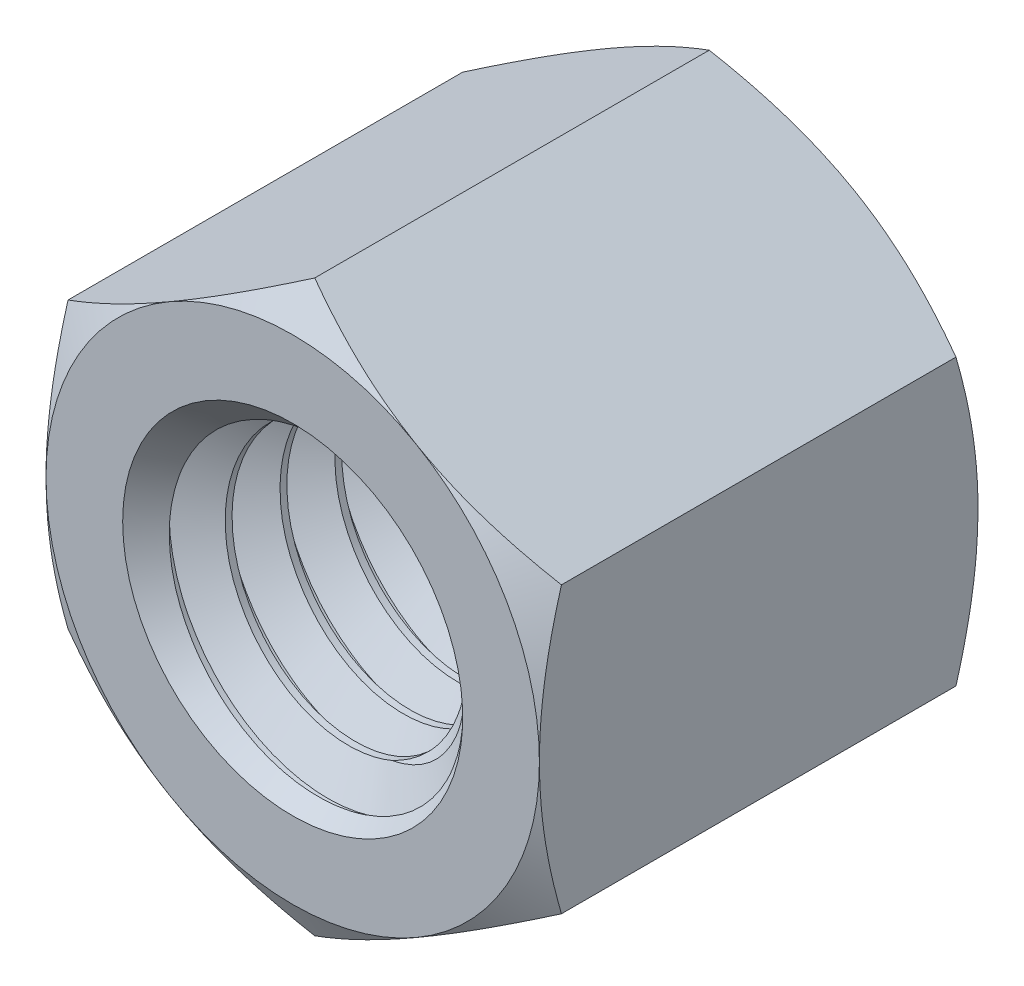
SolidWorks part; units mm, degrees
ref_plane "Front Plane" through (0, 0, 0) normal (0, 0, 1) x (1, 0, 0)
ref_plane "Top Plane" through (0, 0, 0) normal (0, 1, 0) x (1, 0, 0)
ref_plane "Right Plane" through (0, 0, 0) normal (1, 0, 0) x (0, 0, -1)
sketch "Sketch3" plane through (0, 0, 0) normal (1, 0, 0) x (0, 0, -1)
  line L0 (-2, 0) -> (2, 0) construction
  line L1 (0, 2.25) -> (0, -2.25) construction
  line L2 (-2, 1.5) -> (-2, -1.5) construction
  point P2 (-10.7, 0)
  point P3 (10.7, 0)
  dimension "D1" = 12.7
  dimension "Length" = 4
  dimension "Min Thread Length" = 12.7
  dimension "Thread Dia" = 3
  dimension "Hex" = 4.5
sketch "Sketch1" plane through (0, 0, 0) normal (0, 0, 1) x (1, 0, 0)
  line L1 (0, 2.5981) -> (-2.25, 1.299)
  line L2 (-2.25, 1.299) -> (-2.25, -1.299)
  line L3 (-2.25, -1.299) -> (0, -2.5981)
  line L4 (0, -2.5981) -> (2.25, -1.299)
  line L5 (2.25, -1.299) -> (2.25, 1.299)
  line L6 (2.25, 1.299) -> (0, 2.5981)
  circle A0 centre (0, 0) radius 2.25 construction
  circle A1 centre (0, 0) radius 1.5
extrude "Extrude1" add sketch "Sketch1" along normal up to vertex (2 mm away) and the other way up to vertex (2 mm away) up to point (0, 0, 2) other way up to point (0, 0, -2)
sketch "Sketch11" plane through (0, 0, -2) normal (0, 0, -1) x (-1, 0, 0)
  circle A0 centre (0, 0) radius 1.5 construction
  circle A1 centre (0, 0) radius 1.5
curve "Helix/Spiral1" pitch 0.5 height 4.5 radius 1.5 centre (0, 0, -2) axis (0, 0, 1) start towards (0, 1, 0) parameters "Pitch"=0.5
sketch "Sketch12" plane through (0, 0, 0) normal (1, 0, 0) x (0, 0, -1)
  line L0 (2.4375, 1.5) -> (2, 1.5)
  line L1 (2.4375, 1.5) -> (2.25, 1.1752)
  line L2 (2.25, 1.1752) -> (2.1875, 1.1752)
  line L3 (2.1875, 1.1752) -> (2, 1.5)
  line L4 (2.2188, 1.1752) -> (2.2188, 1.5) construction
  line L5 (2.3438, 1.3376) -> (2.0938, 1.3376) construction
  dimension "D1" = 0.0625
  dimension "D2" = 0.25
  dimension "D3" = 60
sweep "Sweep1" add profiles "Sketch12" path "Helix/Spiral1"
sketch "Sketch6" plane through (0, 0, -2) normal (0, 0, -1) x (-1, 0, 0)
  line L6 (0, 2.5981) -> (-2.25, 1.299)
  line L7 (-2.25, 1.299) -> (-2.25, -1.299)
  line L8 (-2.25, -1.299) -> (0, -2.5981)
  line L9 (0, -2.5981) -> (2.25, -1.299)
  line L10 (2.25, -1.299) -> (2.25, 1.299)
  line L11 (2.25, 1.299) -> (0, 2.5981)
  line L12 (0, 2.5981) -> (-2.25, 1.299)
  line L13 (-2.25, 1.299) -> (-2.25, -1.299)
  line L14 (-2.25, -1.299) -> (0, -2.5981)
  line L15 (0, -2.5981) -> (2.25, -1.299)
  line L16 (2.25, -1.299) -> (2.25, 1.299)
  line L17 (2.25, 1.299) -> (0, 2.5981)
  dimension "D1" = 0
extrude "Extrude2" cut sketch "Sketch6" along normal through all
sketch "Sketch7" plane through (0, 0, -2) normal (0, 0, -1) x (-1, 0, 0)
  circle A2 centre (0, 0) radius 1.5508
  circle A3 centre (0, 0) radius 1.5508
  dimension "D1" = 0.0508
extrude "Extrude3" cut sketch "Sketch7" against normal through all draft 43
sketch "Sketch8" plane through (0, 0, -2) normal (0, 0, -1) x (-1, 0, 0)
  circle A0 centre (0, 0) radius 2.25 construction
  circle A1 centre (0, 0) radius 2.25
extrude "Extrude4" cut sketch "Sketch8" against normal through all draft 60 flip side to cut
mirror "Mirror1" about plane through (0, 0, 0) normal (0, 0, 1) of "Extrude2", "Extrude3", "Extrude4"
sketch "Sketch9" [suppressed] plane through (0, 0, 0) normal (1, 0, 0) x (0, 0, -1)
  line L1 (-12.7, 2.4638) -> (12.7, 2.4638)
  line L2 (-12.7, 2.4638) -> (-12.7, 0)
  line L3 (-12.7, 0) -> (12.7, 0)
  line L4 (12.7, 2.4638) -> (12.7, 0)
  line L7 (-25.4, 0) -> (25.4, 0) construction
revolve "Revolve" [suppressed] add sketch "Sketch9" angle 360 about L0
sketch "Sketch10" [suppressed] plane through (0, 0, 0) normal (1, 0, 0) x (0, 0, -1)
  line L0 (25.4, 2.413) -> (12.7, 2.413)
  line L1 (-25.4, 2.413) -> (-12.7, 2.413)
  line L2 (12.7, 2.413) -> (12.7, -2.413)
  line L3 (-25.4, -2.4638) -> (-12.7, -2.4638)
  line L4 (-12.7, 2.413) -> (-12.7, -2.4638)
  line L5 (12.7, -2.413) -> (25.4, -2.413)
sketch "Sketch13" plane through (0, 0, 2) normal (0, 0, 1) x (1, 0, 0)
  line L0 (0.6959, 0.4402) -> (1.0897, 0.4402) construction
  line L1 (0.6959, 0.4402) -> (0.6959, -0.3853) construction
  line L2 (0.6959, 0.4402) -> (3.8103, 3.3481) construction
  arc A0 (0.5013, -1.063) -> (1.1082, -0.3912) centre (0, 0) ccw construction
  point P0 (0.6959, 0.4402)
  point P8 (-11.7542, 6.7404)
  point P9 (3.8103, 3.3481)
  point P10 (3.8103, 3.3481)
  point P11 (1.0897, 0.4402)
equation "\"D1@Sketch3\" = \"Min Thread Length@Sketch3\""
equation "\"D3@Helix/Spiral1\" = \"Length@Sketch3\"+\"Pitch@Helix/Spiral1\""
equation "\"D1@Sketch12\" = \"Pitch@Helix/Spiral1\"*.125"
equation "\"D2@Sketch12\" = \"Pitch@Helix/Spiral1\"*.5"
